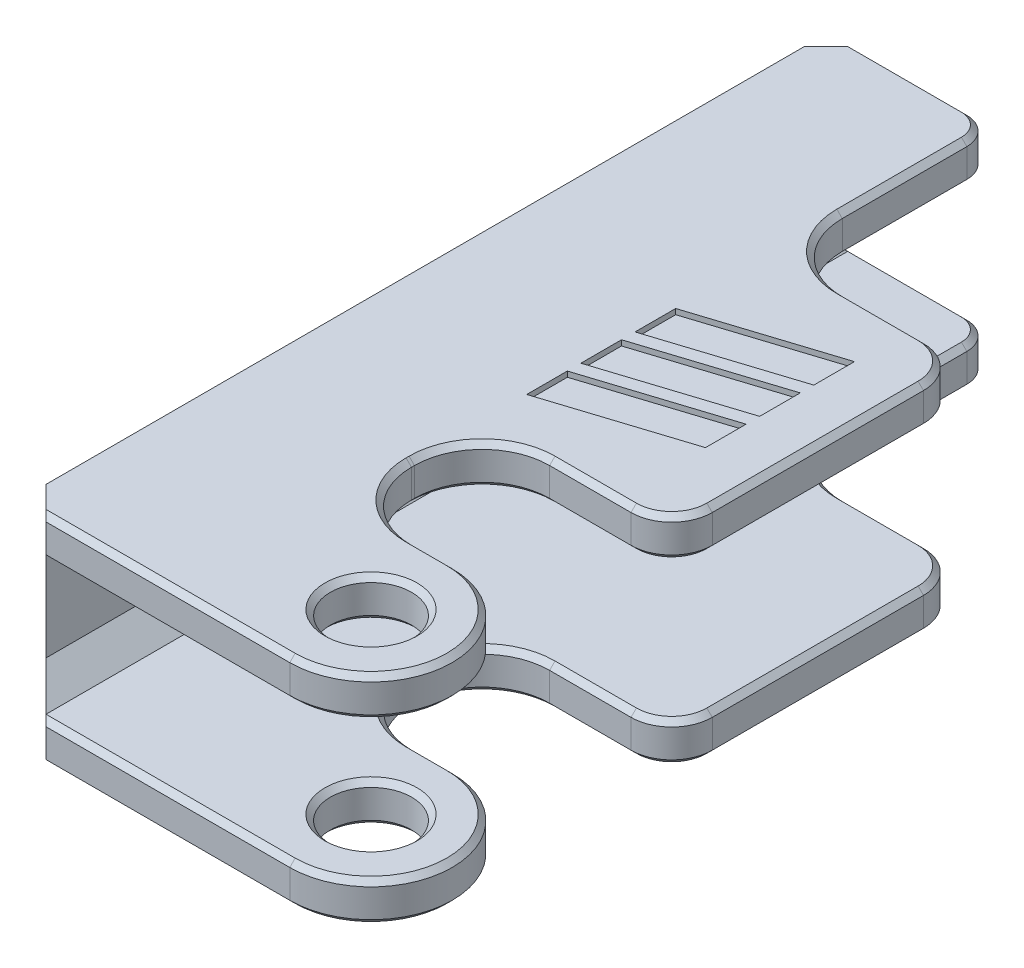
SolidWorks part; units mm, degrees
ref_plane "前视基准面" through (0, 0, 0) normal (0, 0, 1) x (1, 0, 0)
ref_plane "上视基准面" through (0, 0, 0) normal (0, 1, 0) x (1, 0, 0)
ref_plane "右视基准面" through (0, 0, 0) normal (1, 0, 0) x (0, 0, -1)
other "Configuration Table"
sketch "草图1" plane through (0, 0, 0) normal (0, 1, 0) x (1, 0, 0)
  line L1 (0, 0) -> (29, 0)
  line L2 (0, 0) -> (0, 60)
  line L3 (0, 60) -> (29, 60)
  line L4 (29, 0) -> (29, 60)
  dimension "D1" = 60
  dimension "D2" = 29
extrude "凸台-拉伸1" add sketch "草图1" along normal blind 16
sketch "草图2" plane through (0, 0, -60) normal (0, 0, -1) x (-1, 0, 0)
  line L0 (-29, 16) -> (-29, 0) construction
  line L1 (-29, 13.1) -> (-2.8, 13.1)
  line L2 (-29, 13.1) -> (-29, 2.9)
  line L3 (-29, 2.9) -> (-2.8, 2.9)
  line L4 (-2.8, 13.1) -> (-2.8, 2.9)
  line L5 (-29, 16) -> (0, 16) construction
  line L6 (-29, 0) -> (0, 0) construction
  line L7 (0, 16) -> (0, 0) construction
  dimension "D1" = 2.9
  dimension "D2" = 2.9
  dimension "D3" = 2.8
extrude "切除-拉伸1" cut sketch "草图2" against normal through all
sketch "草图3" plane through (0, 0, 0) normal (0, -1, 0) x (-1, 0, 0)
  line L0 (0, 0) -> (-29, 0) construction
  line L1 (0, 60) -> (0, 0) construction
  circle A0 centre (-23, 6) radius 3
  dimension "D1" = 6
  dimension "D2" = 6
  dimension "D3" = 23
extrude "切除-拉伸2" cut sketch "草图3" against normal through all
sketch "草图4" plane through (0, 16, 0) normal (0, 1, 0) x (1, 0, 0)
  line L0 (23, 0) -> (24.9729, -1.2827)
  line L1 (24.9729, -1.2827) -> (32.7443, -1.5862)
  line L2 (32.7443, -1.5862) -> (32.1044, 9.6864)
  line L3 (32.1044, 9.6864) -> (29.9581, 12)
  line L4 (29.9581, 12) -> (23, 12)
  arc A0 (23, 0) -> (23, 12) centre (23, 6) ccw
  dimension "D1" = 12
extrude "切除-拉伸3" cut sketch "草图4" against normal through all
sketch "草图5" plane through (0, 16, 0) normal (0, 1, 0) x (1, 0, 0)
  line L0 (29, 12) -> (29, 60) construction
  line L1 (29, 12) -> (19.99, 12)
  line L2 (29, 12) -> (29, 22.2)
  line L3 (29, 22.2) -> (19.99, 22.2)
  line L4 (15, 16.99) -> (15, 17.21)
  line L5 (29, 12) -> (23, 12) construction
  arc A0 (19.99, 22.2) -> (15, 17.21) centre (19.99, 17.21) ccw
  arc A1 (19.99, 12) -> (15, 16.99) centre (19.99, 16.99) cw
  point P10 (15, 22.2)
  dimension "D3" = 4.99
  dimension "D1" = 10.2
  dimension "D2" = 14
extrude "切除-拉伸4" cut sketch "草图5" against normal through all
sketch "草图6" plane through (0, 16, 0) normal (0, 1, 0) x (1, 0, 0)
  line L0 (29, 60) -> (0, 60) construction
  line L1 (29, 60) -> (15, 60)
  line L2 (29, 60) -> (29, 43.8)
  line L3 (29, 43.8) -> (20, 43.8)
  line L4 (15, 60) -> (15, 48.8)
  line L5 (29, 22.2) -> (29, 60) construction
  line L6 (29, 22.2) -> (19.99, 22.2) construction
  arc A0 (20, 43.8) -> (15, 48.8) centre (20, 48.8) cw
  point P12 (15, 43.8)
  dimension "D4" = 5
  dimension "D1" = 14
  dimension "D2" = 0
  dimension "D3" = 21.6
extrude "切除-拉伸5" cut sketch "草图6" against normal through all
fillet "圆角1" radius 3 4 edges at (29, 14.55, -22.2) (29, 14.55, -43.8) (29, 1.45, -43.8) (29, 1.45, -22.2)
chamfer "倒角1" distance 5 angle 45 2 edges at (0, 8, -60) (0, 8, 0)
chamfer "倒角3" distance 3 angle 45 2 edges at (0, 16, -30) (0, 0, -30)
chamfer "倒角4" distance 1.8 angle 45 2 edges at (2.8, 2.9, -30) (2.8, 13.1, -30)
fillet "圆角2" radius 2 2 edges at (15, 1.45, -60) (15, 14.55, -60)
chamfer "倒角2" distance 0.4 angle 45 64 edges at (23, 0, -9) (29, 0, -6) (21.495, 0, -12) (16.4615, 0, -13.4615) (15, 0, -17.1) (16.4615, 0, -20.7385) (22.995, 0, -22.2) (28.1213, 0, -23.0787) (29, 0, -33) (28.1213, 0, -42.9213) (23, 0, -43.8) (16.4645, 0, -45.2645) (15, 0, -53.4) (9, 0, -60) (14, 0, 0) (29, 13.1, -6) (21.495, 13.1, -12) (16.4615, 13.1, -13.4615) (15, 13.1, -17.1) (16.4615, 13.1, -20.7385) (22.995, 13.1, -22.2) (28.1213, 13.1, -23.0787) (29, 13.1, -33) (28.1213, 13.1, -42.9213) (23, 13.1, -43.8) (16.4645, 13.1, -45.2645) (15, 13.1, -53.4) (9, 13.1, -60) (14, 13.1, 0) (23, 13.1, -3) (9, 2.9, -60) (15, 2.9, -53.4) (16.4645, 2.9, -45.2645) (23, 2.9, -43.8) (28.1213, 2.9, -42.9213) (29, 2.9, -33) (28.1213, 2.9, -23.0787) (22.995, 2.9, -22.2) (16.4615, 2.9, -20.7385) (15, 2.9, -17.1) (16.4615, 2.9, -13.4615) (21.495, 2.9, -12) (29, 2.9, -6) (14, 2.9, 0) (23, 2.9, -9) (9, 16, -60) (15, 16, -53.4) (16.4645, 16, -45.2645) (23, 16, -43.8) (28.1213, 16, -42.9213) (29, 16, -33) (28.1213, 16, -23.0787) (22.995, 16, -22.2) (16.4615, 16, -20.7385) (15, 16, -17.1) (16.4615, 16, -13.4615) (21.495, 16, -12) (29, 16, -6) (14, 16, 0) (23, 16, -9) (14.4142, 0, -59.4142) (14.4142, 13.1, -59.4142) (14.4142, 2.9, -59.4142) (14.4142, 16, -59.4142)
sketch "草图7" plane through (0, 16, 0) normal (0, 1, 0) x (1, 0, 0)
  line L0 (25, 28.7) -> (15, 25.4984)
  line L1 (25, 28.7) -> (25, 31.7)
  line L2 (15, 25.4984) -> (15, 28.4984)
  line L3 (25, 31.7) -> (15, 28.4984)
  line L6 (29, 22.2) -> (29, 43.8) construction
  line L7 (25, 32.7) -> (15, 29.4984)
  line L8 (25, 32.7) -> (25, 35.7)
  line L9 (25, 35.7) -> (15, 32.4984)
  line L10 (15, 29.4984) -> (15, 32.4984)
  line L11 (25, 36.7) -> (15, 33.4984)
  line L12 (25, 36.7) -> (25, 39.7)
  line L13 (25, 39.7) -> (15, 36.4984)
  line L14 (15, 33.4984) -> (15, 36.4984)
  line L15 (29, 22.2) -> (19.99, 22.2) construction
  dimension "D1" = 10.5
  dimension "D2" = 3
  dimension "D3" = 4
  dimension "D4" = 10
  dimension "D6" = 6.5
  dimension "D5" = 3
extrude "切除-拉伸6" cut sketch "草图7" against normal blind 0.4
ref_plane "基准面1" through (0, 8, 0) normal (0, 1, 0) x (1, 0, 0)
mirror "镜向1" about plane through (0, 8, 0) normal (0, 1, 0) of "切除-拉伸6"
equation "\"D3@草图3\"=3+20"
